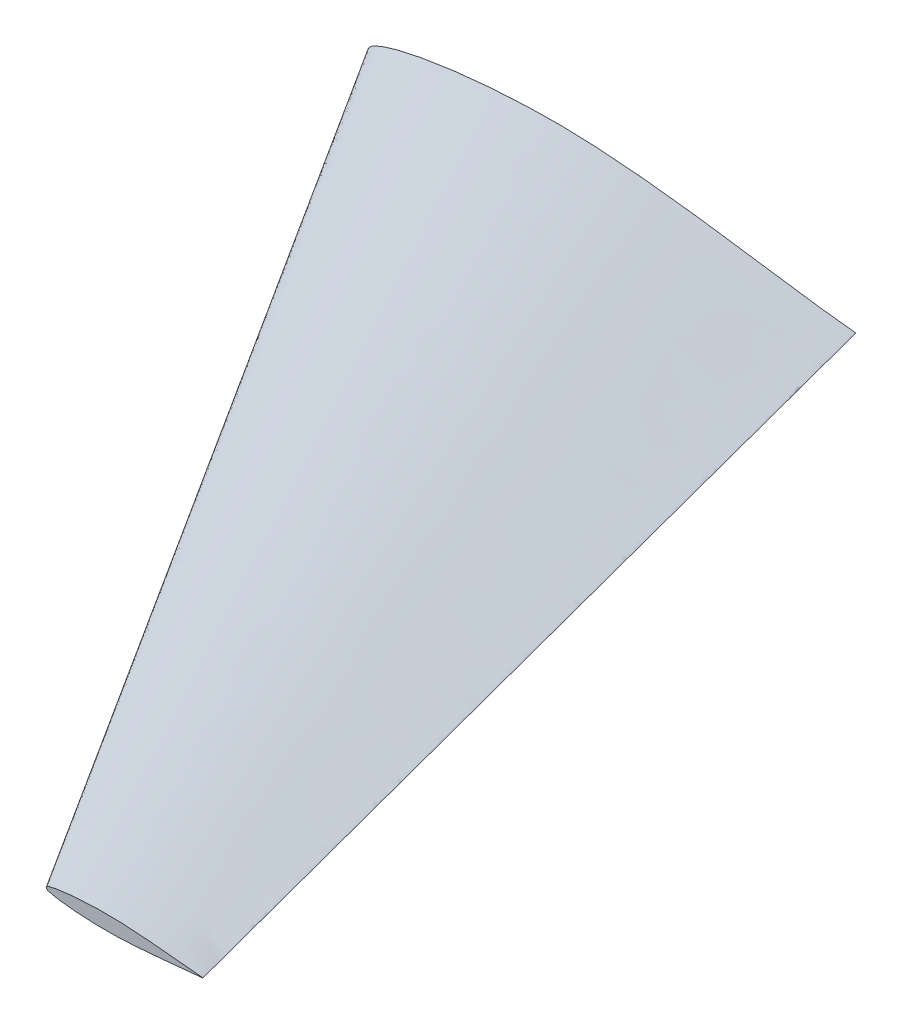
SolidWorks part; units mm, degrees
ref_plane "Alzado" through (0, 0, 0) normal (0, 0, 1) x (1, 0, 0)
ref_plane "Planta" through (0, 0, 0) normal (0, 1, 0) x (1, 0, 0)
ref_plane "Vista lateral" through (0, 0, 0) normal (1, 0, 0) x (0, 0, -1)
curve "Curva1"
  spline degree 3 poles (3330.9062, 5.3107, 0) (3637.7732, -6.6093, 0) (3331.703, 21.175, 0) (3190.2991, 42.7114, 0) (3004.5972, 68.4145, 0) (2830.6233, 94.0667, 0) (2653.312, 119.7373, 0) (2476.6679, 144.1683, 0) (2299.6496, 166.9776, 0) (2122.549, 187.5379, 0) (1945.3041, 205.3361, 0) (1767.9584, 219.8681, 0) (1590.4978, 230.255, 0) (1412.9425, 236.1295, 0) (1235.3447, 234.0216, 0) (1057.8076, 227.7854, 0) (880.2969, 216.2588, 0) (702.8265, 199.6202, 0) (525.3731, 177.3214, 0) (377.7683, 152.6726, 0) (259.9871, 127.5589, 0) (171.2682, 104.876, 0) (97.6696, 80.341, 0) (48.0942, 58.4888, 0) (25.6389, 43.5403, 0) (7.9892, 29.0692, 0) (-8.1877, -0.8616, 0) (13.2485, -26.5108, 0) (32.2445, -38.5406, 0) (55.8788, -50.2342, 0) (106.4809, -66.3384, 0) (180.7992, -83.6767, 0) (269.6997, -99.1933, 0) (387.4505, -116.1461, 0) (534.5516, -132.1436, 0) (710.9862, -146.3898, 0) (887.2513, -156.4154, 0) (1063.4261, -162.8538, 0) (1239.5633, -165.2514, 0) (1415.708, -164.6165, 0) (1591.8285, -157.1588, 0) (1767.9688, -146.2364, 0) (1944.1887, -132.2415, 0) (2120.4977, -116.0235, 0) (2296.9069, -98.1988, 0) (2473.4904, -79.2364, 0) (2649.9843, -59.8569, 0) (2827.4689, -40.894, 0) (3001.9289, -22.8797, 0) (3188.3774, -9.0555, 0) (3330.9062, 5.3107, 0) (3637.7732, -6.6093, 0) (3331.703, 21.175, 0) knots -0.074261 -0.049472 -0.024715 0 0.024745 0.04954 0.074382 0.099256 0.124151 0.149044 0.173926 0.19879 0.223628 0.248438 0.273219 0.297983 0.322733 0.347498 0.372289 0.397132 0.42205 0.44709 0.459702 0.47242 0.485376 0.492121 0.495019 0.496585 0.501771 0.506936 0.508462 0.511288 0.517891 0.530642 0.543183 0.555632 0.580401 0.605064 0.62967 0.654248 0.678802 0.703354 0.72792 0.752528 0.777175 0.801863 0.826588 0.851349 0.876135 0.900935 0.925739 0.950528 0.975285 1 1.024745 1.04954 1.074382 periodic
sketch "Croquis1" plane through (0, 0, 0) normal (0, 0, 1) x (1, 0, 0)
  line L0 (0, 0) -> (50000, 0) construction
  spline S0 degree 3 poles (3330.9062, 5.3107) (3637.7732, -6.6093) (3331.703, 21.175) (3190.2991, 42.7114) (3004.5972, 68.4145) (2830.6233, 94.0667) (2653.312, 119.7373) (2476.6679, 144.1683) (2299.6496, 166.9776) (2122.549, 187.5379) (1945.3041, 205.3361) (1767.9584, 219.8681) (1590.4978, 230.255) (1412.9425, 236.1295) (1235.3447, 234.0216) (1057.8076, 227.7854) (880.2969, 216.2588) (702.8265, 199.6202) (525.3731, 177.3214) (377.7683, 152.6726) (259.9871, 127.5589) (171.2682, 104.876) (97.6696, 80.341) (48.0942, 58.4888) (25.6389, 43.5403) (7.9892, 29.0692) (-8.1877, -0.8616) (13.2485, -26.5108) (32.2445, -38.5406) (55.8788, -50.2342) (106.4809, -66.3384) (180.7992, -83.6767) (269.6997, -99.1933) (387.4505, -116.1461) (534.5516, -132.1436) (710.9862, -146.3898) (887.2513, -156.4154) (1063.4261, -162.8538) (1239.5633, -165.2514) (1415.708, -164.6165) (1591.8285, -157.1588) (1767.9688, -146.2364) (1944.1887, -132.2415) (2120.4977, -116.0235) (2296.9069, -98.1988) (2473.4904, -79.2364) (2649.9843, -59.8569) (2827.4689, -40.894) (3001.9289, -22.8797) (3188.3774, -9.0555) (3330.9062, 5.3107) (3637.7732, -6.6093) (3331.703, 21.175) knots -0.074261 -0.049472 -0.024715 0 0.024745 0.04954 0.074382 0.099256 0.124151 0.149044 0.173926 0.19879 0.223628 0.248438 0.273219 0.297983 0.322733 0.347498 0.372289 0.397132 0.42205 0.44709 0.459702 0.47242 0.485376 0.492121 0.495019 0.496585 0.501771 0.506936 0.508462 0.511288 0.517891 0.530642 0.543183 0.555632 0.580401 0.605064 0.62967 0.654248 0.678802 0.703354 0.72792 0.752528 0.777175 0.801863 0.826588 0.851349 0.876135 0.900935 0.925739 0.950528 0.975285 1 1.024745 1.04954 1.074382 only from (3535.68, 0) to (3535.68, 0) construction
  spline S1 degree 3 poles (3330.9062, 5.3107) (3637.7732, -6.6093) (3331.703, 21.175) (3190.2991, 42.7114) (3004.5972, 68.4145) (2830.6233, 94.0667) (2653.312, 119.7373) (2476.6679, 144.1683) (2299.6496, 166.9776) (2122.549, 187.5379) (1945.3041, 205.3361) (1767.9584, 219.8681) (1590.4978, 230.255) (1412.9425, 236.1295) (1235.3447, 234.0216) (1057.8076, 227.7854) (880.2969, 216.2588) (702.8265, 199.6202) (525.3731, 177.3214) (377.7683, 152.6726) (259.9871, 127.5589) (171.2682, 104.876) (97.6696, 80.341) (48.0942, 58.4888) (25.6389, 43.5403) (7.9892, 29.0692) (-8.1877, -0.8616) (13.2485, -26.5108) (32.2445, -38.5406) (55.8788, -50.2342) (106.4809, -66.3384) (180.7992, -83.6767) (269.6997, -99.1933) (387.4505, -116.1461) (534.5516, -132.1436) (710.9862, -146.3898) (887.2513, -156.4154) (1063.4261, -162.8538) (1239.5633, -165.2514) (1415.708, -164.6165) (1591.8285, -157.1588) (1767.9688, -146.2364) (1944.1887, -132.2415) (2120.4977, -116.0235) (2296.9069, -98.1988) (2473.4904, -79.2364) (2649.9843, -59.8569) (2827.4689, -40.894) (3001.9289, -22.8797) (3188.3774, -9.0555) (3330.9062, 5.3107) (3637.7732, -6.6093) (3331.703, 21.175) knots -0.074261 -0.049472 -0.024715 0 0.024745 0.04954 0.074382 0.099256 0.124151 0.149044 0.173926 0.19879 0.223628 0.248438 0.273219 0.297983 0.322733 0.347498 0.372289 0.397132 0.42205 0.44709 0.459702 0.47242 0.485376 0.492121 0.495019 0.496585 0.501771 0.506936 0.508462 0.511288 0.517891 0.530642 0.543183 0.555632 0.580401 0.605064 0.62967 0.654248 0.678802 0.703354 0.72792 0.752528 0.777175 0.801863 0.826588 0.851349 0.876135 0.900935 0.925739 0.950528 0.975285 1 1.024745 1.04954 1.074382 only from (3535.68, 0) to (3535.68, 0)
ref_plane "Plano1" through (0, 0, 6781.8) normal (0, 0, 1) x (1, 0, 0)
curve "Curva3"
  spline degree 3 poles (1069.44, -5.7872, 0) (1167.7133, 0, 0) (1069.44, 5.7872, 0) (1023.8083, 11.2914, 0) (964.0798, 16.8196, 0) (908.1303, 22.3287, 0) (851.1762, 27.8633, 0) (794.4935, 33.2416, 0) (737.7373, 38.295, 0) (680.995, 42.8174, 0) (624.2461, 46.7193, 0) (567.4981, 49.9069, 0) (510.7455, 52.1619, 0) (453.9857, 53.3234, 0) (397.2246, 52.9456, 0) (340.4683, 51.5548, 0) (283.7092, 49.1304, 0) (238.3168, 46.3206, 0) (204.2821, 43.6606, 0) (181.5813, 41.662, 0) (158.8792, 39.4267, 0) (136.1745, 36.9214, 0) (117.2622, 34.5544, 0) (102.1378, 32.4391, 0) (90.7868, 30.7412, 0) (79.4348, 28.9201, 0) (68.0804, 26.955, 0) (56.7227, 24.8001, 0) (45.361, 22.389, 0) (33.9802, 19.6377, 0) (22.5547, 16.3447, 0) (14.8171, 13.5264, 0) (10.7807, 11.5913, 0) (10.2122, 11.3126, 0) (9.6458, 11.0215, 0) (9.0767, 10.7253, 0) (8.5104, 10.4138, 0) (7.9412, 10.0952, 0) (7.3744, 9.7596, 0) (6.8052, 9.4119, 0) (6.2381, 9.0434, 0) (5.6682, 8.6572, 0) (5.1011, 8.2429, 0) (4.5318, 7.8028, 0) (3.9615, 7.329, 0) (3.3916, 6.8112, 0) (2.9241, 6.3415, 0) (2.5474, 5.9382, 0) (2.2655, 5.6081, 0) (1.9779, 5.2575, 0) (1.6955, 4.8746, 0) (1.4059, 4.4576, 0) (1.1222, 3.9874, 0) (0.8311, 3.4491, 0) (0.5316, 2.7888, 0) (0.1458, 1.6508, 0) (-0.1016, 0, 0) (0.1458, -1.6508, 0) (0.5316, -2.7888, 0) (0.8311, -3.4491, 0) (1.1222, -3.9874, 0) (1.4059, -4.4576, 0) (1.6955, -4.8746, 0) (1.9779, -5.2575, 0) (2.2655, -5.6081, 0) (2.5474, -5.9382, 0) (2.9241, -6.3415, 0) (3.3916, -6.8112, 0) (3.9615, -7.329, 0) (4.5318, -7.8028, 0) (5.1011, -8.2429, 0) (5.6682, -8.6572, 0) (6.2381, -9.0434, 0) (6.8052, -9.4119, 0) (7.3744, -9.7596, 0) (7.9412, -10.0952, 0) (8.5104, -10.4138, 0) (9.0767, -10.7253, 0) (9.6458, -11.0215, 0) (10.2122, -11.3126, 0) (10.7807, -11.5913, 0) (14.8171, -13.5264, 0) (22.5547, -16.3447, 0) (33.9802, -19.6377, 0) (45.361, -22.389, 0) (56.7227, -24.8001, 0) (68.0804, -26.955, 0) (79.4348, -28.9201, 0) (90.7868, -30.7412, 0) (102.1378, -32.4391, 0) (117.2622, -34.5544, 0) (136.1745, -36.9214, 0) (158.8792, -39.4267, 0) (181.5813, -41.662, 0) (204.2821, -43.6606, 0) (238.3168, -46.3206, 0) (283.7092, -49.1304, 0) (340.4683, -51.5548, 0) (397.2246, -52.9456, 0) (453.9857, -53.3234, 0) (510.7455, -52.1619, 0) (567.4981, -49.9069, 0) (624.2461, -46.7193, 0) (680.995, -42.8174, 0) (737.7373, -38.295, 0) (794.4935, -33.2416, 0) (851.1762, -27.8633, 0) (908.1303, -22.3287, 0) (964.0798, -16.8196, 0) (1023.8083, -11.2914, 0) (1069.44, -5.7872, 0) (1167.7133, 0, 0) (1069.44, 5.7872, 0) knots -0.074601 -0.049738 -0.024873 0 0.024873 0.049738 0.074601 0.099464 0.124327 0.149183 0.174026 0.198851 0.223655 0.24844 0.273206 0.297957 0.322703 0.347457 0.372227 0.397022 0.40695 0.416887 0.426834 0.436793 0.44677 0.451768 0.456772 0.461785 0.466808 0.471847 0.476908 0.482002 0.487159 0.492465 0.492739 0.493015 0.493293 0.493573 0.493855 0.494139 0.494426 0.494716 0.495011 0.495311 0.495617 0.49593 0.496252 0.496586 0.496937 0.497119 0.497308 0.497505 0.497712 0.49793 0.498168 0.49843 0.498731 0.499116 0.5 0.500884 0.501269 0.50157 0.501832 0.50207 0.502288 0.502495 0.502692 0.502881 0.503063 0.503414 0.503748 0.50407 0.504383 0.504689 0.504989 0.505284 0.505574 0.505861 0.506145 0.506427 0.506707 0.506985 0.507261 0.507535 0.512841 0.517998 0.523092 0.528153 0.533192 0.538215 0.543228 0.548232 0.55323 0.563207 0.573166 0.583113 0.59305 0.602978 0.627773 0.652543 0.677297 0.702043 0.726794 0.75156 0.776345 0.801149 0.825974 0.850817 0.875673 0.900536 0.925399 0.950262 0.975127 1 1.024873 1.049738 1.074601 periodic
sketch "Croquis5" plane through (0, 0, 6781.8) normal (0, 0, 1) x (1, 0, 0)
  spline S1 degree 3 poles (5522.568, 365.6726) (5620.8413, 371.4598) (5522.568, 377.247) (5476.9363, 382.7511) (5417.2078, 388.2794) (5361.2583, 393.7884) (5304.3042, 399.3231) (5247.6215, 404.7014) (5190.8653, 409.7548) (5134.123, 414.2772) (5077.3741, 418.179) (5020.6261, 421.3666) (4963.8735, 423.6217) (4907.1137, 424.7831) (4850.3526, 424.4053) (4793.5963, 423.0145) (4736.8372, 420.5902) (4691.4448, 417.7804) (4657.4101, 415.1203) (4634.7093, 413.1218) (4612.0072, 410.8864) (4589.3025, 408.3811) (4570.3902, 406.0142) (4555.2658, 403.8989) (4543.9148, 402.201) (4532.5628, 400.3799) (4521.2084, 398.4147) (4509.8507, 396.2599) (4498.489, 393.8488) (4487.1082, 391.0975) (4475.6827, 387.8044) (4467.9451, 384.9862) (4463.9087, 383.051) (4463.3402, 382.7724) (4462.7738, 382.4812) (4462.2047, 382.1851) (4461.6384, 381.8736) (4461.0692, 381.5549) (4460.5024, 381.2193) (4459.9332, 380.8716) (4459.3661, 380.5031) (4458.7962, 380.117) (4458.2291, 379.7027) (4457.6598, 379.2626) (4457.0895, 378.7887) (4456.5196, 378.271) (4456.0521, 377.8012) (4455.6754, 377.398) (4455.3935, 377.0679) (4455.1059, 376.7172) (4454.8235, 376.3344) (4454.5339, 375.9174) (4454.2502, 375.4472) (4453.9591, 374.9089) (4453.6596, 374.2486) (4453.2738, 373.1106) (4453.0264, 371.4598) (4453.2738, 369.809) (4453.6596, 368.6709) (4453.9591, 368.0106) (4454.2502, 367.4723) (4454.5339, 367.0021) (4454.8235, 366.5852) (4455.1059, 366.2023) (4455.3935, 365.8516) (4455.6754, 365.5215) (4456.0521, 365.1183) (4456.5196, 364.6485) (4457.0895, 364.1308) (4457.6598, 363.657) (4458.2291, 363.2168) (4458.7962, 362.8025) (4459.3661, 362.4164) (4459.9332, 362.0479) (4460.5024, 361.7002) (4461.0692, 361.3646) (4461.6384, 361.0459) (4462.2047, 360.7345) (4462.7738, 360.4383) (4463.3402, 360.1471) (4463.9087, 359.8685) (4467.9451, 357.9334) (4475.6827, 355.1151) (4487.1082, 351.822) (4498.489, 349.0707) (4509.8507, 346.6597) (4521.2084, 344.5048) (4532.5628, 342.5396) (4543.9148, 340.7186) (4555.2658, 339.0207) (4570.3902, 336.9053) (4589.3025, 334.5384) (4612.0072, 332.0331) (4634.7093, 329.7977) (4657.4101, 327.7992) (4691.4448, 325.1392) (4736.8372, 322.3294) (4793.5963, 319.905) (4850.3526, 318.5142) (4907.1137, 318.1364) (4963.8735, 319.2979) (5020.6261, 321.5529) (5077.3741, 324.7405) (5134.123, 328.6423) (5190.8653, 333.1647) (5247.6215, 338.2181) (5304.3042, 343.5965) (5361.2583, 349.1311) (5417.2078, 354.6401) (5476.9363, 360.1684) (5522.568, 365.6726) (5620.8413, 371.4598) (5522.568, 377.247) knots -0.074601 -0.049738 -0.024873 0 0.024873 0.049738 0.074601 0.099464 0.124327 0.149183 0.174026 0.198851 0.223655 0.24844 0.273206 0.297957 0.322703 0.347457 0.372227 0.397022 0.40695 0.416887 0.426834 0.436793 0.44677 0.451768 0.456772 0.461785 0.466808 0.471847 0.476908 0.482002 0.487159 0.492465 0.492739 0.493015 0.493293 0.493573 0.493855 0.494139 0.494426 0.494716 0.495011 0.495311 0.495617 0.49593 0.496252 0.496586 0.496937 0.497119 0.497308 0.497505 0.497712 0.49793 0.498168 0.49843 0.498731 0.499116 0.5 0.500884 0.501269 0.50157 0.501832 0.50207 0.502288 0.502495 0.502692 0.502881 0.503063 0.503414 0.503748 0.50407 0.504383 0.504689 0.504989 0.505284 0.505574 0.505861 0.506145 0.506427 0.506707 0.506985 0.507261 0.507535 0.512841 0.517998 0.523092 0.528153 0.533192 0.538215 0.543228 0.548232 0.55323 0.563207 0.573166 0.583113 0.59305 0.602978 0.627773 0.652543 0.677297 0.702043 0.726794 0.75156 0.776345 0.801149 0.825974 0.850817 0.875673 0.900536 0.925399 0.950262 0.975127 1 1.024873 1.049738 1.074601 only from (5588.08, 371.4598) to (5588.08, 371.4598)
loft "Recubrir1" add profiles "Croquis1", "Croquis5" connector at (0.6087, -3.6743, 0) connector at (4453.8125, 374.5797, 6781.8)
ref_plane "Plano2" through (0, 0, 10) normal (0, 0, 1) x (1, 0, 0)
sketch "Croquis7" plane through (0, 0, 0) normal (0, 0, 1) x (1, 0, 0)
  line L0 (0, 0) -> (50000, 0) construction
ref_axis "Eje1" through (0, 0, 0) along (1, 0, 0)
